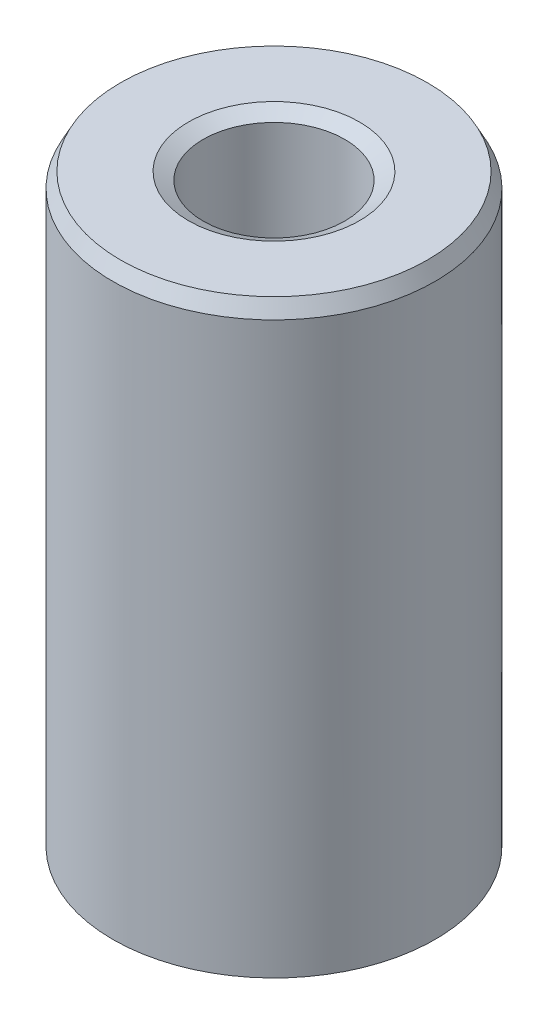
SolidWorks part; units mm, degrees
ref_plane "Front Plane" through (0, 0, 0) normal (0, 0, 1) x (1, 0, 0)
ref_plane "Top Plane" through (0, 0, 0) normal (0, 1, 0) x (1, 0, 0)
ref_plane "Right Plane" through (0, 0, 0) normal (1, 0, 0) x (0, 0, -1)
sketch "Sketch1" plane through (0, 0, 0) normal (0, 1, 0) x (1, 0, 0)
  circle A0 centre (0, 0) radius 15
  dimension "SLEEVE_OD" = 30
extrude "Boss-Extrude1" add sketch "Sketch1" along normal blind 55.1129
sketch "Sketch2" plane through (0, 0, 0) normal (0, 1, 0) x (1, 0, 0)
  circle A0 centre (0, 0) radius 6.5906
  dimension "BORE_D" = 13.1813
extrude "Cut-Extrude1" cut sketch "Sketch2" along normal through all
chamfer "Chamfer1" distance 1.3692 angle 27.582 4 edges at (0, 55.1129, 6.5906) (0, 0, 6.5906) (0, 0, 15) (0, 55.1129, 15) first distance on face at (0, 55.1129, 6.5906) first distance on face at (0, 0, 6.5906) first distance on face at (0, 55.1129, 15)
